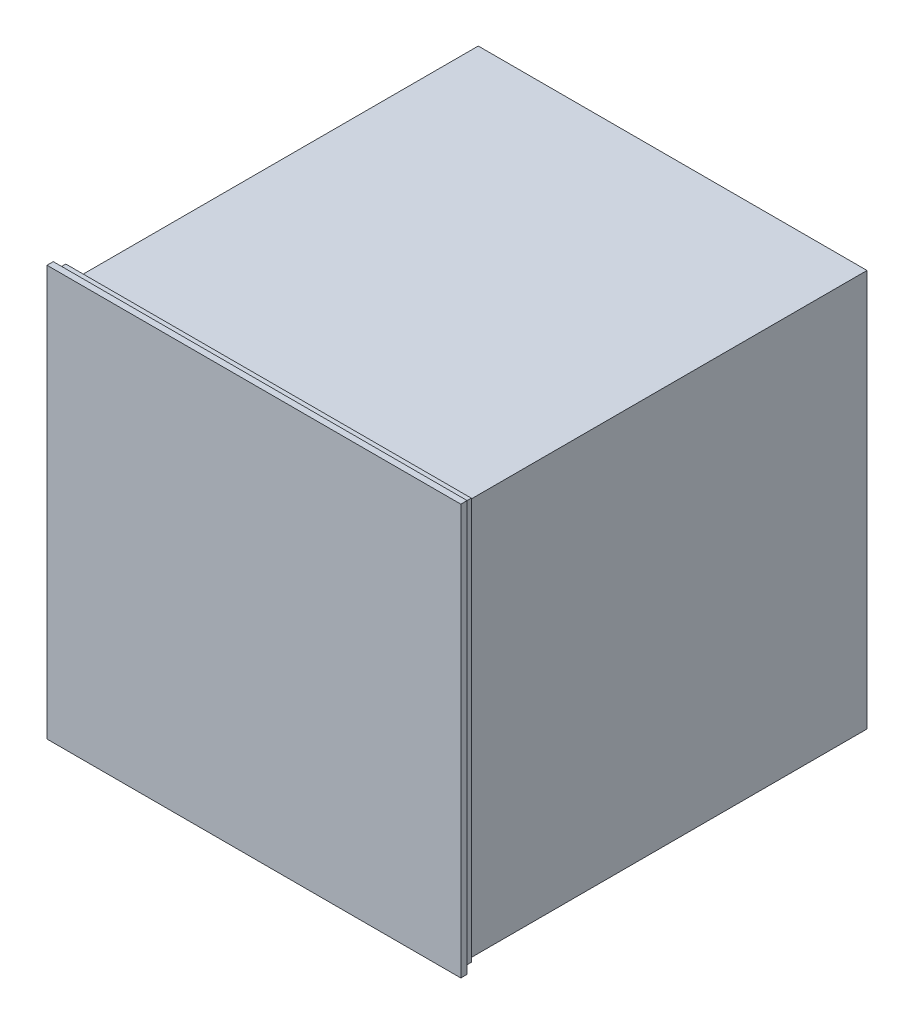
SolidWorks part; units mm, degrees
ref_plane "Спереди" through (0, 0, 0) normal (0, 0, 1) x (1, 0, 0)
ref_plane "Сверху" through (0, 0, 0) normal (0, 1, 0) x (1, 0, 0)
ref_plane "Справа" through (0, 0, 0) normal (1, 0, 0) x (0, 0, -1)
sketch "Эскиз1" plane through (0, 0, 0) normal (0, 0, 1) x (1, 0, 0)
  line L1 (-291, 288.5) -> (291, 288.5)
  line L2 (-291, 288.5) -> (-291, -288.5)
  line L3 (-291, -288.5) -> (291, -288.5)
  line L4 (291, 288.5) -> (291, -288.5)
  line L5 (-291, 288.5) -> (291, -288.5) construction
  line L6 (-291, -288.5) -> (291, 288.5) construction
  point P0 (0, 0)
extrude "Бобышка-Вытянуть1" add sketch "Эскиз1" along normal blind 12
sketch "Эскиз2" plane through (0, 0, 0) normal (0, 0, -1) x (-1, 0, 0)
  line L1 (-279, 275.5) -> (279, 275.5)
  line L2 (-279, 275.5) -> (-279, -294.5)
  line L3 (-279, -294.5) -> (279, -294.5)
  line L4 (279, 275.5) -> (279, -294.5)
  point P4 (0, 0)
  point P5 (0, 0)
  point P6 (0, 0)
  point P7 (0, 0)
  point P10 (0, 0)
  point P12 (0, 0)
  point P13 (0, 0)
  point P15 (0, 0)
  point P16 (0, 0)
extrude "Бобышка-Вытянуть2" add sketch "Эскиз2" along normal blind 580
sketch "Эскиз3" plane through (0, 0, 12) normal (0, 0, 1) x (1, 0, 0)
  line L1 (-297, 294.5) -> (297, 294.5)
  line L2 (-297, 294.5) -> (-297, -294.5)
  line L3 (-297, -294.5) -> (297, -294.5)
  line L4 (297, 294.5) -> (297, -294.5)
  line L5 (-297, 294.5) -> (297, -294.5) construction
  line L6 (-297, -294.5) -> (297, 294.5) construction
  point P0 (0, 0)
extrude "Бобышка-Вытянуть3" add sketch "Эскиз3" along normal blind 9
